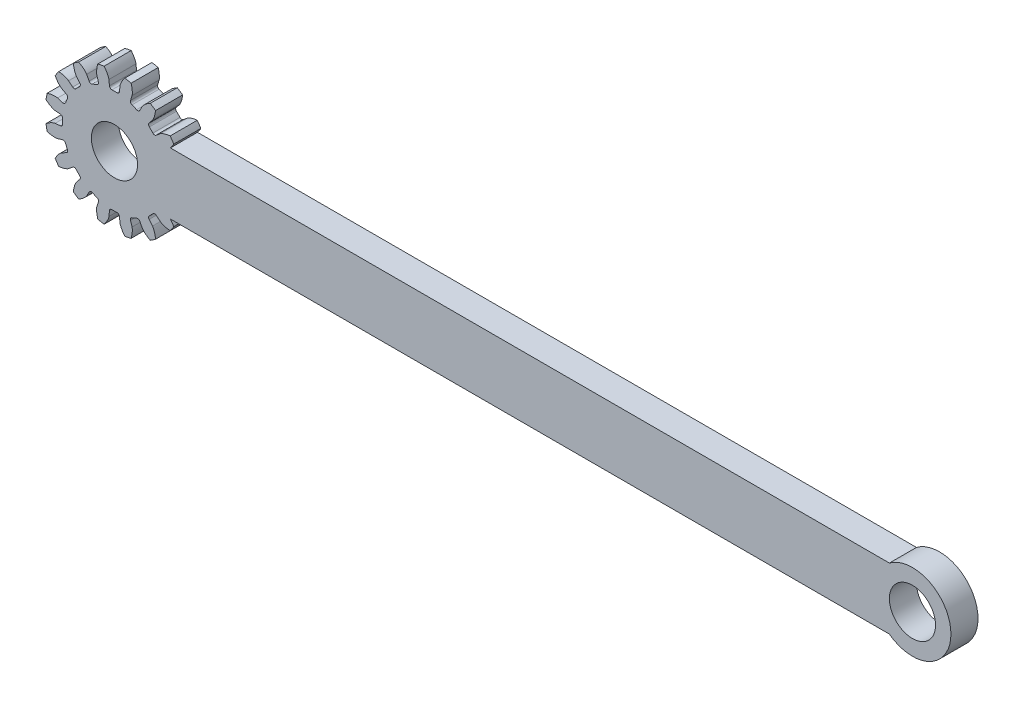
SolidWorks part; units mm, degrees
ref_plane "Front Plane" through (0, 0, 0) normal (0, 0, 1) x (1, 0, 0)
ref_plane "Top Plane" through (0, 0, 0) normal (0, 1, 0) x (1, 0, 0)
ref_plane "Right Plane" through (0, 0, 0) normal (1, 0, 0) x (0, 0, -1)
sketch "Sketch1" plane through (0, 0, 0) normal (0, 0, 1) x (1, 0, 0)
  line L1 (12.7988, -6.35) -> (159.9195, -6.35)
  line L3 (12.7988, 6.35) -> (159.9195, 6.35)
  arc A1 (159.9195, -6.35) -> (159.9195, 6.35) centre (164.682, 0) ccw
  arc A2 (12.7988, 6.35) -> (12.7988, -6.35) centre (0, 0) ccw
  point P1 (0, 0)
  dimension "D4" = 15.875
  dimension "D2" = 28.575
  dimension "D1" = 12.7
extrude "Boss-Extrude1" add sketch "Sketch1" along normal blind 5.588
sketch "Sketch3" plane through (0, 0, 5.588) normal (0, 0, 1) x (1, 0, 0)
  line L0 (0, 0) -> (10.6697, 0.9912) construction
  line L1 (10.6697, 0.9912) -> (12.2428, 1.1373)
  line L2 (0, 0) -> (10.6697, -0.9912) construction
  line L3 (10.6697, -0.9912) -> (12.2428, -1.1373)
  circle A0 centre (0, 0) radius 14.2875 construction
  circle A1 centre (0, 0) radius 12.7 construction
  circle A2 centre (0, 0) radius 12.2955 construction
  circle A3 centre (0, 0) radius 10.7156 construction
  arc A6 (10.6697, 0.9912) -> (10.6697, -0.9912) centre (0, 0) cw
  arc A7 (14.1269, 2.1361) -> (14.1269, -2.1361) centre (0, 0) cw
  spline S0 degree 4 poles (12.2428, 1.1373) (12.2459, 1.1376) (12.2548, 1.1387) (12.2715, 1.1412) (12.2987, 1.1459) (12.3332, 1.153) (12.3777, 1.1633) (12.4298, 1.1769) (12.4868, 1.1934) (12.5485, 1.213) (12.6098, 1.234) (12.6707, 1.2564) (12.7311, 1.2799) (12.8039, 1.3098) (12.8907, 1.3478) (12.9915, 1.395) (13.1049, 1.452) (13.2195, 1.5138) (13.3315, 1.5775) (13.4435, 1.6454) (13.5513, 1.7135) (13.662, 1.7877) (13.7637, 1.858) (13.8763, 1.9405) (13.9669, 2.0083) (14.0849, 2.1017) (14.1541, 2.158) (14.2346, 2.2254) (14.2701, 2.256) (14.292, 2.2749) knots 0 0 0 0 0 0.005377 0.015084 0.028532 0.04661 0.064855 0.092111 0.119476 0.146842 0.174209 0.201575 0.228941 0.256307 0.307035 0.361767 0.4165 0.471232 0.525964 0.580697 0.635429 0.690161 0.744894 0.799626 0.854358 0.909091 0.954545 1 1 1 1 1 construction
  spline S1 degree 4 poles (12.2428, 1.1373) (12.2459, 1.1376) (12.2548, 1.1387) (12.2715, 1.1412) (12.2987, 1.1459) (12.3332, 1.153) (12.3777, 1.1633) (12.4298, 1.1769) (12.4868, 1.1934) (12.5485, 1.213) (12.6098, 1.234) (12.6707, 1.2564) (12.7311, 1.2799) (12.8039, 1.3098) (12.8907, 1.3478) (12.9915, 1.395) (13.1049, 1.452) (13.2195, 1.5138) (13.3315, 1.5775) (13.4435, 1.6454) (13.5513, 1.7135) (13.662, 1.7877) (13.7637, 1.858) (13.8763, 1.9405) (13.9669, 2.0083) (14.0593, 2.0814) (14.1041, 2.1175) (14.1269, 2.1361) knots 0 0 0 0 0 0.005377 0.015084 0.028532 0.04661 0.064855 0.092111 0.119476 0.146842 0.174209 0.201575 0.228941 0.256307 0.307035 0.361767 0.4165 0.471232 0.525964 0.580697 0.635429 0.690161 0.744894 0.799626 0.854358 0.909091 0.909091 0.909091 0.909091 0.909091
  spline S2 degree 4 poles (12.2428, -1.1373) (12.2459, -1.1376) (12.2548, -1.1387) (12.2715, -1.1412) (12.2987, -1.1459) (12.3332, -1.153) (12.3777, -1.1633) (12.4298, -1.1769) (12.4868, -1.1934) (12.5485, -1.213) (12.6098, -1.234) (12.6707, -1.2564) (12.7311, -1.2799) (12.8039, -1.3098) (12.8907, -1.3478) (12.9915, -1.395) (13.1049, -1.452) (13.2195, -1.5138) (13.3315, -1.5775) (13.4435, -1.6454) (13.5513, -1.7135) (13.662, -1.7877) (13.7637, -1.858) (13.8763, -1.9405) (13.9669, -2.0083) (14.0849, -2.1017) (14.1541, -2.158) (14.2346, -2.2254) (14.2701, -2.256) (14.292, -2.2749) knots 0 0 0 0 0 0.005377 0.015084 0.028532 0.04661 0.064855 0.092111 0.119476 0.146842 0.174209 0.201575 0.228941 0.256307 0.307035 0.361767 0.4165 0.471232 0.525964 0.580697 0.635429 0.690161 0.744894 0.799626 0.854358 0.909091 0.954545 1 1 1 1 1 construction
  spline S3 degree 4 poles (12.2428, -1.1373) (12.2459, -1.1376) (12.2548, -1.1387) (12.2715, -1.1412) (12.2987, -1.1459) (12.3332, -1.153) (12.3777, -1.1633) (12.4298, -1.1769) (12.4868, -1.1934) (12.5485, -1.213) (12.6098, -1.234) (12.6707, -1.2564) (12.7311, -1.2799) (12.8039, -1.3098) (12.8907, -1.3478) (12.9915, -1.395) (13.1049, -1.452) (13.2195, -1.5138) (13.3315, -1.5775) (13.4435, -1.6454) (13.5513, -1.7135) (13.662, -1.7877) (13.7637, -1.858) (13.8763, -1.9405) (13.9669, -2.0083) (14.0593, -2.0814) (14.1041, -2.1175) (14.1269, -2.1361) knots 0 0 0 0 0 0.005377 0.015084 0.028532 0.04661 0.064855 0.092111 0.119476 0.146842 0.174209 0.201575 0.228941 0.256307 0.307035 0.361767 0.4165 0.471232 0.525964 0.580697 0.635429 0.690161 0.744894 0.799626 0.854358 0.909091 0.909091 0.909091 0.909091 0.909091
  dimension "D1" = 28.575
  dimension "D2" = 25.4
  dimension "D3" = 24.591
  dimension "D4" = 21.4312
extrude "Cut-Extrude1" cut sketch "Sketch3" against normal through all
fillet "Fillet1" radius 0.4962 2 edges at (10.6697, 0.9912, 2.794) (10.6697, -0.9912, 2.794)
pattern_circular "CirPattern1" count 16 over 360 about axis through (0, 0, 5.588) along (0, 0, 1) of "Fillet1", "Cut-Extrude1"
ref_plane "Plane1" through (10.16, 0, 0) normal (1, 0, 0) x (0, 0, -1)
sketch "Sketch4" plane through (10.16, 0, 0) normal (1, 0, 0) x (0, 0, -1)
  line L6 (0, 6.35) -> (-5.588, 6.35)
  line L8 (0, 6.35) -> (0, -6.35)
  line L9 (0, -6.35) -> (-5.588, -6.35)
  line L10 (-5.588, 6.35) -> (-5.588, -6.35)
  line L11 (0, 6.35) -> (-5.588, -6.35) construction
  line L12 (0, -6.35) -> (-5.588, 6.35) construction
  point P0 (-2.794, 0)
  dimension "D1" = 5.588
  dimension "D2" = 12.7
extrude "Boss-Extrude2" add sketch "Sketch4" against normal mid plane 10.16
sketch "Sketch5" plane through (0, 0, 5.588) normal (0, 0, 1) x (1, 0, 0)
  circle A0 centre (0, 0) radius 4.7625
  circle A1 centre (164.682, 0) radius 4.7625
  dimension "D1" = 9.525
extrude "Cut-Extrude2" cut sketch "Sketch5" against normal through all
equation "\"DiametralPitch\" = 16"
equation "\"NumTeeth\"= 16"
equation "\"PressureAngle\"= 14.5deg"
equation "\"Addendum\"= 1 / \"DiametralPitch\""
equation "\"Dedendum\"= 1.25 / \"DiametralPitch\""
equation "\"WorkingDepth\"= 2 / \"DiametralPitch\""
equation "\"WholeDepth\"= 2.25 / \"DiametralPitch\""
equation "\"Clearance\"= 0.25 / \"DiametralPitch\""
equation "\"ToothThickness\"= 1.5708 / \"DiametralPitch\""
equation "\"CircularPitch\"= pi / \"DiametralPitch\""
equation "\"PitchCircle\"= \"NumTeeth\" / \"DiametralPitch\""
equation "\"OutsideDiameter\"= ( \"NumTeeth\" + 2 ) / \"DiametralPitch\""
equation "\"Fillet\"= \"Clearance\" * cos ( \"PressureAngle\" ) * tan ( ( 90 + \"PressureAngle\" ) / 2 )"
equation "\"AddendumCircle\"= \"PitchCircle\" + ( 2 * \"Addendum\" )"
equation "\"DedendumCircle\"= \"PitchCircle\" - ( 2 * \"Dedendum\" )"
equation "\"BaseCircle\"= \"PitchCircle\" * cos ( \"PressureAngle\" )"
equation "\"PitchAngle\"= 360deg / \"NumTeeth\""
equation "\"Alpha\"= sqr ( \"PitchCircle\" ^ 2 - \"BaseCircle\" ^ 2 ) / \"BaseCircle\" * 180 / PI - \"PressureAngle\""
equation "\"Beta\"= ( \"PitchAngle\" / 4 - \"Alpha\" )"
equation "\"Phi\"= sqr ( ( \"AddendumCircle\" / 2 ) ^ 2 - ( \"BaseCircle\" / 2 ) ^ 2 ) / ( \"BaseCircle\" / 2 )"
equation "\"D2@Sketch1\"= \"OutsideDiameter\""
equation "\"D1@Sketch3\"=\"OutsideDiameter\""
equation "\"D2@Sketch3\"=\"PitchCircle\""
equation "\"D3@Sketch3\"=\"BaseCircle\""
equation "\"D4@Sketch3\"=\"DedendumCircle\""
equation "\"D1@Fillet1\"=\"Fillet\""
equation "\"D1@CirPattern1\"=\"NumTeeth\""
